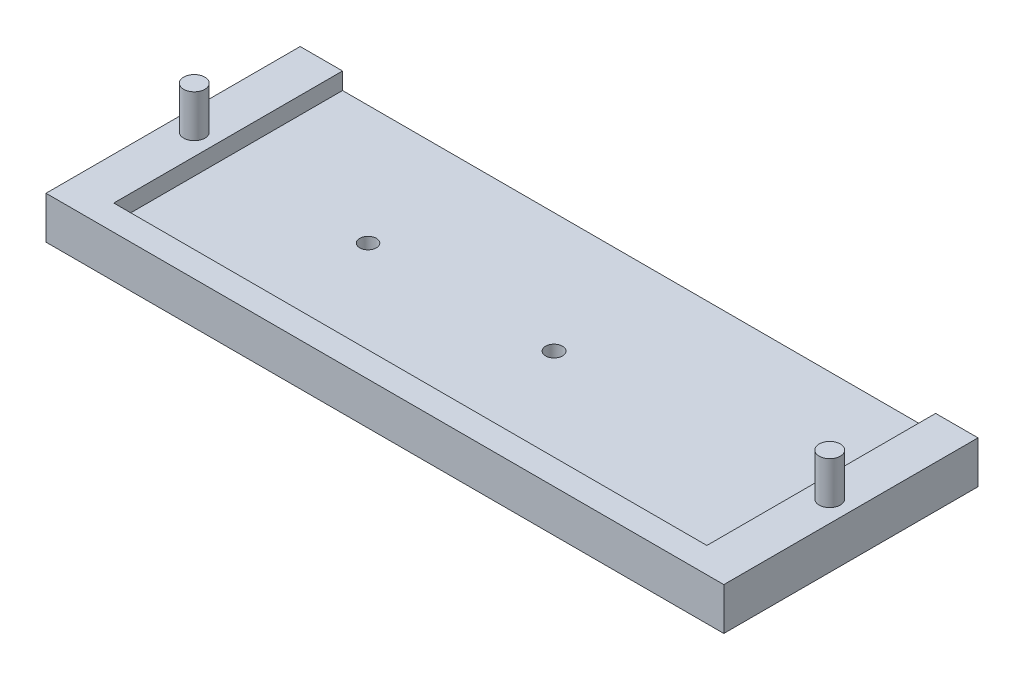
SolidWorks part; units mm, degrees
ref_plane "Front Plane" through (0, 0, 0) normal (0, 0, 1) x (1, 0, 0)
ref_plane "Top Plane" through (0, 0, 0) normal (0, 1, 0) x (1, 0, 0)
ref_plane "Right Plane" through (0, 0, 0) normal (1, 0, 0) x (0, 0, -1)
sketch "Sketch1" plane through (0, 0, 0) normal (0, 1, 0) x (1, 0, 0)
  line L1 (-45.72, 30.0703) -> (157.48, 30.0703)
  line L2 (-45.72, 30.0703) -> (-45.72, -46.1297)
  line L3 (-45.72, -46.1297) -> (157.48, -46.1297)
  line L4 (157.48, 30.0703) -> (157.48, -46.1297)
  dimension "D1" = 76.2
  dimension "D2" = 203.2
extrude "Boss-Extrude1" add sketch "Sketch1" along normal blind 12.7 contours L2 L3 L4 L1
sketch "Sketch2" plane through (0, 12.7, 0) normal (0, 1, 0) x (1, 0, 0)
  line L0 (157.48, 30.0703) -> (157.48, -46.1297) construction
  line L1 (-33.02, 30.0703) -> (144.78, 30.0703)
  line L2 (-33.02, 30.0703) -> (-33.02, -38.5097)
  line L3 (-33.02, -38.5097) -> (144.78, -38.5097)
  line L4 (144.78, 30.0703) -> (144.78, -38.5097)
  line L5 (-33.02, 30.0703) -> (144.78, -38.5097) construction
  line L6 (-33.02, -38.5097) -> (144.78, 30.0703) construction
  line L7 (-45.72, -46.1297) -> (157.48, -46.1297) construction
  point P0 (55.88, -4.2197)
  dimension "D1" = 177.8
  dimension "D2" = 68.58
  dimension "D3" = 12.7
  dimension "D4" = 7.62
extrude "Cut-Extrude1" cut sketch "Sketch2" against normal blind 5.08
sketch "Sketch3" plane through (0, 12.7, 0) normal (0, 1, 0) x (1, 0, 0)
  line L0 (157.48, 30.0703) -> (157.48, -46.1297) construction
  line L1 (144.78, 30.0703) -> (157.48, 30.0703) construction
  circle A0 centre (151.13, -8.0297) radius 3.175
  dimension "D2" = 6.35
  dimension "D1" = 6.35
  dimension "D3" = 38.1
extrude "Boss-Extrude3" add sketch "Sketch3" along normal blind 12.7
sketch "Sketch4" plane through (0, 12.7, 0) normal (0, 1, 0) x (1, 0, 0)
  line L0 (-45.72, 30.0703) -> (-45.72, -46.1297) construction
  line L1 (-45.72, -46.1297) -> (157.48, -46.1297) construction
  circle A0 centre (-39.37, -8.0297) radius 3.175
  dimension "D1" = 6.35
  dimension "D2" = 6.35
  dimension "D3" = 38.1
extrude "Boss-Extrude4" add sketch "Sketch4" along normal blind 12.7
sketch "Sketch5" plane through (0, 0, 0) normal (0, -1, 0) x (1, 0, 0)
  text T0 "FoodLocker" font "Biondi" height in points 72
extrude "Boss-Extrude6" add sketch "Sketch5" along normal blind 1.27
sketch "Sketch6" plane through (0, 0, 0) normal (0, -1, 0) x (1, 0, 0)
  circle A0 centre (10.4049, 5.7145) radius 2.4892
  spline S0 degree 3 poles (14.5466, 5.7829) (14.5433, 5.8996) (14.5368, 6.1299) (14.4725, 6.469) (14.3744, 6.7977) (14.2349, 7.1134) (14.0666, 7.4166) (13.8593, 7.6969) (13.6297, 7.963) (13.3657, 8.2044) (13.078, 8.4273) (12.7625, 8.6266) (12.4199, 8.7982) (12.0556, 8.9508) (11.6689, 9.0703) (11.2647, 9.1594) (10.8442, 9.2124) (10.558, 9.2182) (10.4131, 9.2211) knots 0 0 0 0 0.05861 0.115734 0.173024 0.230808 0.288993 0.347061 0.405841 0.465512 0.52662 0.588751 0.652841 0.719161 0.787224 0.856098 0.927141 1 1 1 1 construction
  point P2 (13.2044, 8.3275)
  dimension "D1" = 4.9784
  dimension "D2" = 3.8295
extrude "Cut-Extrude2" cut sketch "Sketch6" against normal blind 2.54
extrude "Cut-Extrude3" cut sketch "Sketch6<2>" against normal blind 25.4
sketch "Sketch6<2>" plane through (0, 0, 0) normal (0, -1, 0) x (1, 0, 0) same geometry as "Sketch6"
sketch "Sketch7" plane through (0, 0, 0) normal (0, -1, 0) x (1, 0, 0)
  circle A0 centre (66.3204, 5.8678) radius 2.54
  dimension "D1" = 5.08
  dimension "D2" = 3.81
extrude "Cut-Extrude4" cut sketch "Sketch7" against normal blind 25.4
